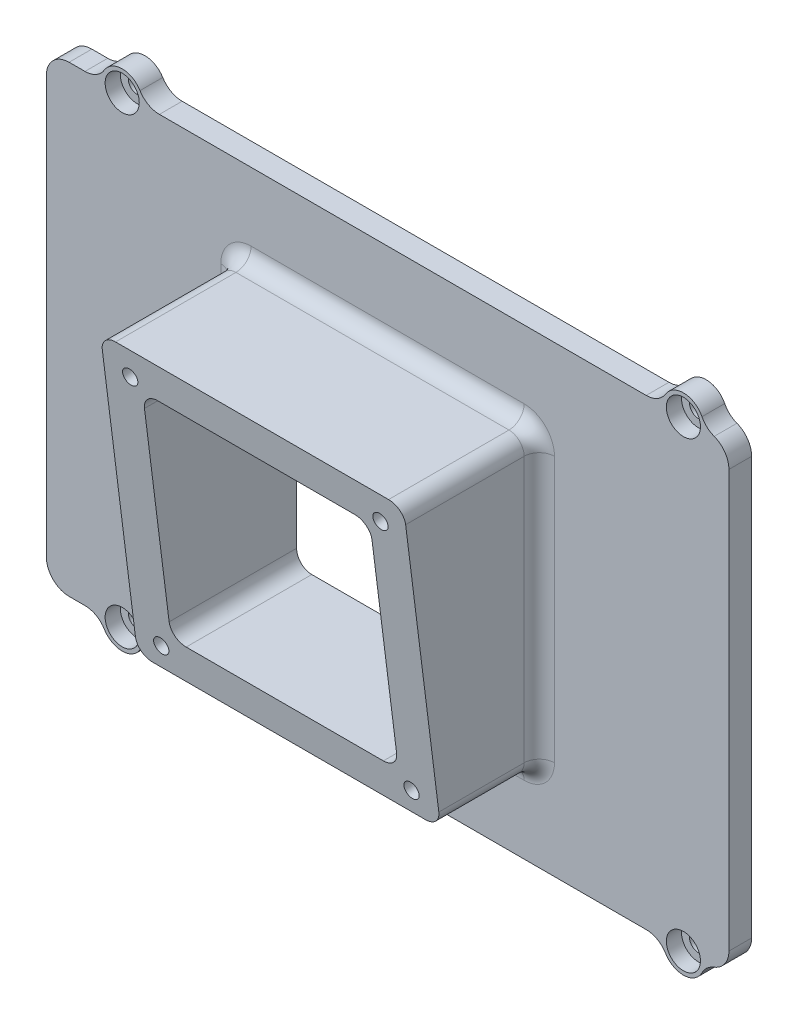
SolidWorks part; units mm, degrees
ref_plane "Спереди" through (0, 0, 0) normal (0, 0, 1) x (1, 0, 0)
ref_plane "Сверху" through (0, 0, 0) normal (0, 1, 0) x (1, 0, 0)
ref_plane "Справа" through (0, 0, 0) normal (1, 0, 0) x (0, 0, -1)
sketch "Эскиз1" plane through (0, 0, 0) normal (0, 1, 0) x (1, 0, 0)
  line L0 (0, 45) -> (0, -45) construction
  line L1 (-30.5, 45) -> (30.5, 45)
  line L2 (-30.5, 45) -> (-30.5, -45)
  line L3 (-30.5, -45) -> (30.5, -45)
  line L4 (30.5, 45) -> (30.5, -45)
  line L6 (-30.5, 0) -> (30.5, 0) construction
  point P8 (0, 0)
  dimension "D1" = 90
  dimension "D2" = 61
extrude "боковые стенки" [suppressed] add sketch "Эскиз1" along normal blind 18
sketch "Эскиз7" plane through (0, 0, 0) normal (0, 1, 0) x (1, 0, 0)
  line L1 (-30.5, 45) -> (30.5, 45)
  line L2 (-30.5, 45) -> (-30.5, -45)
  line L3 (-30.5, -45) -> (30.5, -45)
  line L4 (30.5, 45) -> (30.5, -45)
extrude "крышка" [suppressed] add sketch "Эскиз7" along normal blind 12
dome "Купол6" [suppressed] faces to dome 1 distance 10 parameters "D1"=10
shell "Оболочка1" [suppressed] thickness 2
sketch "Эскиз11" [suppressed] plane through (-30.5, 0, 0) normal (-1, 0, 0) x (0, 0, 1)
  line L1 (-45, 30) -> (45, 30) construction
  line L2 (0, 30) -> (45, 30)
  line L4 (45, 30) -> (45, 18)
  ellipse E0 centre (0, 18) end of major axis (-45, 18) minor radius 12 (45, 18) -> (0, 30) ccw
  dimension "D1" = 12
extrude "скругление вдоль" [suppressed] cut sketch "Эскиз11" against normal through all
sketch "Эскиз12" [suppressed] plane through (0, 0, -45) normal (0, 0, -1) x (-1, 0, 0)
  line L0 (-30.5, 30) -> (-30.5, 0) construction
  line L1 (-30.5, 18) -> (-30.5, 30)
  line L2 (-30.5, 30) -> (30.5, 30) construction
  line L3 (-30.5, 30) -> (0, 30)
  ellipse E0 centre (0, 18) end of major axis (-30.5, 18) minor radius 12 (0, 30) -> (-30.5, 18) ccw
  dimension "D1" = 12
extrude "скругление поперек" [suppressed] cut sketch "Эскиз12" against normal through all
mirror "Зеркальное отражение3" [suppressed] about plane through (0, 0, 0) normal (0, 0, 1)
mirror "Зеркальное отражение4" [suppressed] about plane through (0, 0, 0) normal (1, 0, 0)
shell "Оболочка5" [suppressed] thickness 2.1
sketch "Эскиз13" [suppressed] plane through (30.5, 0, 0) normal (1, 0, 0) x (0, 0, -1)
  line L0 (-45, 30) -> (-45, 0) construction
  line L1 (-36.15, 1) -> (-27.65, 1)
  line L2 (-36.15, 1) -> (-36.15, 0)
  line L3 (-36.15, 0) -> (-27.65, 0)
  line L4 (-27.65, 1) -> (-27.65, 0)
  line L5 (-45, 0) -> (45, 0) construction
  dimension "D1" = 8.5
  dimension "D3" = 8.85
  dimension "D4" = 1
extrude "отверстие для microusb" [suppressed] cut sketch "Эскиз13" against normal up to surface (2.1 mm away)
sketch "Эскиз14" [suppressed] plane through (30.5, 0, 0) normal (1, 0, 0) x (0, 0, -1)
  line L0 (-45, 30) -> (-45, 0) construction
  line L1 (-18.5, 4.5) -> (-2.5, 4.5)
  line L2 (-18.5, 4.5) -> (-18.5, 0)
  line L3 (-18.5, 0) -> (-2.5, 0)
  line L4 (-2.5, 4.5) -> (-2.5, 0)
  line L5 (-45, 0) -> (-36.15, 0) construction
  line L6 (-27.65, 0) -> (45, 0) construction
  dimension "D1" = 16
  dimension "D3" = 26.5
  dimension "D4" = 4.5
extrude "отверстие для hdmi" [suppressed] cut sketch "Эскиз14" against normal up to surface (2.1 mm away)
sketch "Эскиз15" [suppressed] plane through (30.5, 0, 0) normal (1, 0, 0) x (0, 0, -1)
  line L0 (-45, 30) -> (-45, 0) construction
  line L1 (-2.5, 0) -> (45, 0) construction
  circle A0 centre (11, 0.1) radius 3.5
  dimension "D1" = 7
  dimension "D2" = 56
  dimension "D3" = 0.1
extrude "отверстие для audio" [suppressed] cut sketch "Эскиз15" against normal up to surface (2.1 mm away)
sketch "Эскиз16" [suppressed] plane through (0, 0, -45) normal (0, 0, -1) x (-1, 0, 0)
  line L0 (-30.5, 0) -> (30.5, 0) construction
  line L1 (-26.5, 0) -> (-9, 0)
  line L2 (-26.5, 0) -> (-26.5, 11.5)
  line L3 (-26.5, 11.5) -> (-9, 11.5)
  line L4 (-9, 0) -> (-9, 11.5)
  line L5 (-30.5, 30) -> (-30.5, 0) construction
  dimension "D1" = 4
  dimension "D2" = 11.5
  dimension "D3" = 17.5
extrude "отверстие для ethernet" [suppressed] cut sketch "Эскиз16" against normal up to surface (2.1 mm away)
sketch "Эскиз17" [suppressed] plane through (0, 0, -45) normal (0, 0, -1) x (-1, 0, 0)
  line L0 (-9, 0) -> (30.5, 0) construction
  line L1 (-9, 14) -> (26.75, 14)
  line L2 (-9, 14) -> (-9, 0)
  line L3 (-9, 0) -> (26.75, 0)
  line L4 (26.75, 14) -> (26.75, 0)
  dimension "D2" = 35.75
  dimension "D3" = 14
extrude "отверстие для usb" [suppressed] cut sketch "Эскиз17" against normal up to surface (2.1 mm away)
sketch "Эскиз21" [suppressed] plane through (0, 0, 0) normal (0, 1, 0) x (1, 0, 0)
  line L0 (6.5, 0.5) -> (25.5, 0.5)
  line L1 (6.5, 3.5) -> (25.5, 3.5)
  line L3 (-30.5, -45) -> (30.5, -45) construction
  arc A0 (6.5, 3.5) -> (6.5, 0.5) centre (6.5, 2) ccw
  arc A1 (25.5, 0.5) -> (25.5, 3.5) centre (25.5, 2) ccw
  point P1 (5, 2)
  point P3 (27, 2)
  dimension "D1" = 3
  dimension "D2" = 22
  dimension "D3" = 5
  dimension "D4" = 47
extrude "отверстие для шлейфа камеры" [suppressed] cut sketch "Эскиз21" along normal through all
fillet "Скругление2" [suppressed] radius 1.5
sketch "Эскиз23" [suppressed] plane through (0, 0, 0) normal (0, -1, 0) x (1, 0, 0)
  line L0 (-33, 27) -> (-30.5, 27)
  line L1 (-33, 23) -> (0, 23) construction
  line L2 (-33, 23) -> (-33, 0) construction
  line L3 (-33, 0) -> (0, 0) construction
  line L4 (0, 23) -> (0, 0) construction
  line L5 (-30.5, -43.5) -> (-30.5, 43.5) construction
  line L6 (-30.5, 27) -> (-30.5, 19)
  line L7 (-30.5, 19) -> (-33, 19)
  line L8 (-30.5, -19) -> (-33, -19)
  line L9 (-30.5, -27) -> (-30.5, -19)
  line L10 (-33, -27) -> (-30.5, -27)
  line L11 (33, -27) -> (30.5, -27)
  line L12 (30.5, -27) -> (30.5, -19)
  line L13 (30.5, -19) -> (33, -19)
  line L14 (30.5, 36.15) -> (33, 36.15)
  line L15 (30.5, 43.5) -> (30.5, 36.15)
  line L16 (33, 43.5) -> (30.5, 43.5)
  line L17 (28.4, 36.15) -> (30.5, 36.15) construction
  line L18 (30.5, 45) -> (30.5, 36.15) construction
  circle A0 centre (-33, 23) radius 1.65
  arc A1 (-33, 27) -> (-33, 19) centre (-33, 23) ccw
  arc A2 (-33, -27) -> (-33, -19) centre (-33, -23) cw
  circle A3 centre (-33, -23) radius 1.65
  circle A4 centre (33, -23) radius 1.65
  arc A5 (33, -27) -> (33, -19) centre (33, -23) ccw
  arc A6 (33, 43.5) -> (33, 36.15) centre (33, 39.825) cw
  circle A7 centre (33, 39.825) radius 1.65
  dimension "D3" = 3.3
  dimension "D4" = 8
  dimension "D1" = 33
  dimension "D2" = 23
extrude "крепление к корпусу" [suppressed] add sketch "Эскиз23" against normal blind 5
sketch "Эскиз25" [suppressed] plane through (30.5, 0, 0) normal (1, 0, 0) x (0, 0, -1)
  line L0 (-43.5, 18) -> (43.5, 18) construction
  line L1 (-34.5, 18) -> (15.5, 18)
  line L2 (-34.5, 18) -> (-34.5, 0)
  line L3 (-34.5, 0) -> (15.5, 0)
  line L4 (15.5, 18) -> (15.5, 0)
  line L5 (-43.5, 18) -> (-43.5, 5) construction
  line L6 (42.9, 0) -> (-42.9, 0) construction
  dimension "D1" = 9
  dimension "D2" = 50
extrude "Вырез под Г-образные выводы" [suppressed] cut sketch "Эскиз25" against normal up to next
ref_plane "Плоскость1" [suppressed] through (0, 30, 0) normal (0, 1, 0) x (1, 0, 0)
sketch "Эскиз27" [suppressed] plane through (0, 30, 0) normal (0, 1, 0) x (1, 0, 0)
  line L1 (-2.77, -37) -> (19.73, -37)
  line L2 (-2.77, -37) -> (-2.77, -45)
  line L3 (-2.77, -45) -> (19.73, -45)
  line L4 (19.73, -37) -> (19.73, -45)
  line L6 (30.5, -43.5) -> (30.5, -36.15) construction
  line L7 (29, -45) -> (-29, -45) construction
  dimension "D1" = 8
  dimension "D2" = 22.5
  dimension "D3" = 10.77
extrude "Вырез под клемники (подвод питания для серв и шилда)" [suppressed] cut sketch "Эскиз27" against normal up to next
sketch "Эскиз29" plane through (0, 0, 0) normal (0, 0, 1) x (1, 0, 0)
  line L1 (-45, 30.5) -> (45, 30.5)
  line L2 (-45, 30.5) -> (-45, -30.5)
  line L3 (-45, -30.5) -> (45, -30.5)
  line L4 (45, 30.5) -> (45, -30.5)
  point P5 (0, -30.5)
  point P7 (45, 0)
  dimension "D1" = 90
  dimension "D2" = 61
extrude "Основа крышки" add sketch "Эскиз29" along normal mid plane 3
sketch "Эскиз30" plane through (0, 0, 1.5) normal (0, 0, 1) x (1, 0, 0)
  line L0 (45, 30.5) -> (-45, 30.5) construction
  line L5 (45, -30.5) -> (45, 30.5) construction
  line L6 (36.5, 8.75) -> (40.5, 8.75)
  line L7 (36.5, 8.75) -> (36.5, 0.75)
  line L8 (36.5, 0.75) -> (40.5, 0.75)
  line L9 (40.5, 8.75) -> (40.5, 0.75)
  point P6 (36.5, 4.75)
  dimension "D1" = 8
  dimension "D2" = 4
  dimension "D3" = 4.5
  dimension "D4" = 25.75
extrude "Под винты клеммника" [suppressed] cut sketch "Эскиз30" against normal up to next
sketch "Эскиз31" plane through (0, 0, 1.5) normal (0, 0, 1) x (1, 0, 0)
  line L1 (-12.75, 25.5) -> (8.75, 25.5)
  line L2 (-12.75, 25.5) -> (-12.75, 21.5)
  line L3 (-12.75, 21.5) -> (8.75, 21.5)
  line L4 (8.75, 25.5) -> (8.75, 21.5)
  line L5 (45, 30.5) -> (-45, 30.5) construction
  line L6 (-45, 30.5) -> (-45, -30.5) construction
  point P4 (-2, 25.5)
  dimension "D1" = 21.5
  dimension "D2" = 43
  dimension "D3" = 4
  dimension "D4" = 5
extrude "Под шлейф камеры" [suppressed] cut sketch "Эскиз31" against normal through all
sketch "Эскиз32" plane through (0, 0, 1.5) normal (0, 0, 1) x (1, 0, 0)
  line L1 (45, 30.5) -> (-45, 30.5) construction
  line L2 (45, -30.5) -> (45, 30.5) construction
  circle A0 centre (2, 0.5) radius 3
  dimension "D1" = 6
  dimension "D2" = 30
  dimension "D3" = 43
extrude "Под кнопку RESET" [suppressed] cut sketch "Эскиз32" against normal through all
fillet "Скругление3" radius 3 4 edges at (-45, -30.5, 0) (-45, 30.5, 0) (45, 30.5, 0) (45, -30.5, 0)
sketch "Эскиз33" plane through (0, 0, 1.5) normal (0, 0, 1) x (1, 0, 0)
  line L0 (-45, 0) -> (0, 0) construction
  line L1 (-45, 27.5) -> (-45, -27.5) construction
  line L2 (0, 0) -> (0, -30.5) construction
  line L3 (-42, -30.5) -> (42, -30.5) construction
  line L4 (-37.75, -30.5) -> (-32.25, -30.5)
  line L5 (-37.75, 30.5) -> (-32.25, 30.5)
  line L6 (41.75, -30.5) -> (36.25, -30.5)
  line L7 (45, -27.5) -> (45, 27.5) construction
  line L11 (36.25, 30.5) -> (41.75, 30.5)
  line L13 (42, 30.5) -> (-42, 30.5) construction
  arc A0 (-37.75, -30.5) -> (-32.25, -30.5) centre (-35, -30.5) ccw
  arc A1 (-37.75, 30.5) -> (-32.25, 30.5) centre (-35, 30.5) cw
  arc A2 (41.75, -30.5) -> (36.25, -30.5) centre (39, -30.5) cw
  arc A4 (36.25, 30.5) -> (41.75, 30.5) centre (39, 30.5) cw
  point P33 (39, 30.5)
  point P35 (39, -30.5)
  dimension "D1" = 2.75
  dimension "D3" = 6
  dimension "D2" = 10
extrude "Наплывы под шурупы для крепления с корпусом" add sketch "Эскиз33" against normal up to surface (3 mm away) up to face at (0, 0, -1.5)
sketch "Эскиз34" plane through (0, 0, 1.5) normal (0, 0, 1) x (1, 0, 0)
  circle A0 centre (-35, -30.5) radius 1.2
  circle A1 centre (39, -30.5) radius 1.2
  circle A3 centre (-35, 30.5) radius 1.2
  circle A4 centre (39, 30.5) radius 1.2
  arc A7 (41.75, 30.5) -> (36.25, 30.5) centre (39, 30.5) ccw construction
  dimension "D1" = 2.4
extrude "Отверстия под шурупы для крепления с корпусом" cut sketch "Эскиз34" against normal up to next
sketch "Эскиз35" plane through (0, 0, 1.5) normal (0, 0, 1) x (1, 0, 0)
  circle A0 centre (-35, -30.5) radius 2.25
  circle A1 centre (-35, 30.5) radius 2.25
  circle A3 centre (39, -30.5) radius 2.25
  circle A5 centre (39, 30.5) radius 2.25
  dimension "D1" = 4.5
extrude "Углубления под шляпки" cut sketch "Эскиз35" against normal blind 2
fillet "Скругление под шлейф" [suppressed] radius 2
fillet "Скругление5" [suppressed] radius 2
sketch "Эскиз39" plane through (0, 0, 1.5) normal (0, 0, 1) x (1, 0, 0)
  line L2 (45, -27.5) -> (45, 27.5) construction
  line L3 (-32.25, -30.5) -> (36.25, -30.5) construction
  circle A0 centre (16.5, -4) radius 12.5
  dimension "D1" = 25
  dimension "D2" = 28.5
  dimension "D3" = 26.5
extrude "Под вентилятор" [suppressed] cut sketch "Эскиз39" against normal up to next
sketch "Эскиз36" plane through (0, 0, 1.5) normal (0, 0, 1) x (1, 0, 0)
  line L1 (-20, 19.5) -> (20, 19.5)
  line L2 (-20, 19.5) -> (-20, -19.5)
  line L3 (-20, -19.5) -> (20, -19.5)
  line L4 (20, 19.5) -> (20, -19.5)
  line L5 (-15, 15) -> (15, 15)
  line L6 (-15, 15) -> (-15, -15)
  line L7 (-15, -15) -> (15, -15)
  line L8 (15, 15) -> (15, -15)
  line L11 (-45, 27.5) -> (-45, -27.5) construction
  point P12 (-15, 0)
  point P13 (-20, 0)
  point P18 (0, 15)
  point P20 (0, 19.5)
  point P21 (15, 0)
  point P22 (20, 0)
  dimension "D1" = 39
  dimension "D2" = 40
  dimension "D3" = 30
  dimension "D4" = 45
extrude "Выступ для крепления дисплея" add sketch "Эскиз36" along normal blind 18
chamfer "Фаска2" distance 5 distance2 40 1 edges at (0, -19.5, 19.5) first distance on face at (0, -19.5, 10.5)
sketch "Эскиз37" plane through (0, -2.0846, 16.6769) normal (0, -0.124, 0.9923) x (1, 0, 0)
  line L0 (-16.5, 18.2526) -> (16.5, -14.7474) construction
  line L1 (-16.5, 18.2526) -> (16.5, 18.2526) construction
  line L2 (-16.5, 18.2526) -> (-16.5, -14.7474) construction
  line L3 (-16.5, -14.7474) -> (16.5, -14.7474) construction
  line L4 (16.5, 18.2526) -> (16.5, -14.7474) construction
  line L5 (-16.5, -14.7474) -> (16.5, 18.2526) construction
  line L10 (20, -17.5509) -> (-20, -17.5509) construction
  line L12 (20, 21.7526) -> (-20, 21.7526) construction
  circle A0 centre (-16.5, 18.2526) radius 1
  circle A1 centre (16.5, 18.2526) radius 1
  circle A2 centre (16.5, -14.7474) radius 1
  circle A3 centre (-16.5, -14.7474) radius 1
  point P12 (0, -14.7474)
  point P13 (0, 1.7526)
  point P23 (0, 1.7526)
  point P25 (0, -17.5509)
  dimension "D1" = 2
  dimension "D2" = 33
  dimension "D4" = 3.5
  dimension "D3" = 4
extrude "Отверстия для креплени дисплея в корпусе" cut sketch "Эскиз37" against normal blind 10
sketch "Эскиз38" plane through (0, 0, 1.5) normal (0, 0, 1) x (1, 0, 0)
  line L0 (15, -15) -> (15, 15) construction
  line L1 (-15, 15) -> (15, 15)
  line L2 (-15, 15) -> (-15, -15)
  line L3 (-15, -15) -> (15, -15)
  line L4 (15, 15) -> (15, -15)
  line L5 (15, 15) -> (-15, 15) construction
  point P4 (0, 15)
  point P9 (0, 15)
extrude "Под провод дисплея" cut sketch "Эскиз38" against normal up to next
fillet "Скругление6" radius 2 4 edges at (15, -15, 6.7812) (15, 15, 8.6562) (-15, 15, 8.6562) (-15, -15, 6.7812)
fillet "Скругление7" radius 2 4 edges at (-20, -19.5, 8) (20, -19.5, 8) (20, 19.5, 10.4375) (-20, 19.5, 10.4375)
fillet "Скругление8" radius 3 8 edges at (-37.75, 30.5, 0) (-32.25, 30.5, 0) (36.25, -30.5, 0) (41.75, -30.5, 0) (-32.25, -30.5, 0) (-37.75, -30.5, 0) (36.25, 30.5, 0) (41.75, 30.5, 0)
sketch "Эскиз40" plane through (0, 0, 1.5) normal (0, 0, 1) x (1, 0, 0)
  line L0 (-45, 27.5) -> (-45, -27.5) construction
  line L1 (34.0946, 30.5) -> (-30.0946, 30.5) construction
  line L3 (0, 30.5) -> (0, -30.5) construction
  line L4 (-30.0946, -30.5) -> (34.0946, -30.5) construction
  circle A0 centre (-40, 22.5) radius 1 construction
  circle A1 centre (-40, 7.5) radius 1 construction
  circle A2 centre (-40, -7.5) radius 1 construction
  circle A3 centre (-40, -22.5) radius 1 construction
  circle A4 centre (-25, 22.5) radius 1 construction
  circle A5 centre (-25, 7.5) radius 1 construction
  circle A6 centre (-25, -7.5) radius 1 construction
  circle A7 centre (-25, -22.5) radius 1 construction
  circle A8 centre (25, -22.5) radius 1
  circle A9 centre (25, -7.5) radius 1
  circle A10 centre (25, 7.5) radius 1
  circle A11 centre (25, 22.5) radius 1
  circle A12 centre (40, -22.5) radius 1
  circle A13 centre (40, -7.5) radius 1
  circle A15 centre (40, 22.5) radius 1
  dimension "D1" = 2
  dimension "D5" = 15
  dimension "D2" = 5
  dimension "D3" = 8
  dimension "D6" = 2
  dimension "D7" = 15
  dimension "D4" = 4
extrude "Вентиляционные отверстия" [suppressed] cut sketch "Эскиз40" against normal through all
fillet "Скругление9" radius 2 8 edges at (-19.4142, 18.9142, 1.5) (0, 19.5, 1.5) (19.4142, 18.9142, 1.5) (20, 0, 1.5) (19.4142, -18.9142, 1.5) (0, -19.5, 1.5) (-19.4142, -18.9142, 1.5) (-20, 0, 1.5)
